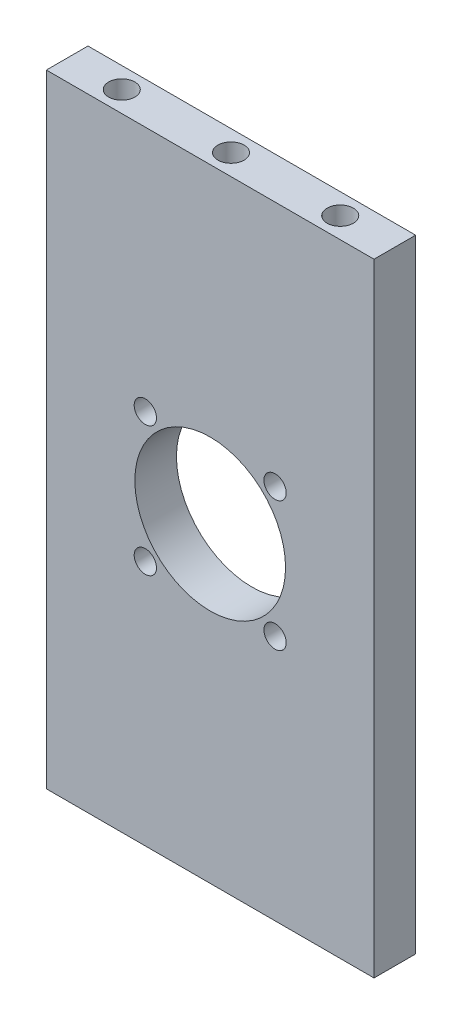
SolidWorks part; units mm, degrees
ref_plane "Front Plane" through (0, 0, 0) normal (0, 0, 1) x (1, 0, 0)
ref_plane "Top Plane" through (0, 0, 0) normal (0, 1, 0) x (1, 0, 0)
ref_plane "Right Plane" through (0, 0, 0) normal (1, 0, 0) x (0, 0, -1)
sketch "Sketch1" plane through (0, 0, 0) normal (0, 0, 1) x (1, 0, 0)
  line L1 (-25, -47.5) -> (25, -47.5)
  line L2 (-25, -47.5) -> (-25, 47.5)
  line L3 (-25, 47.5) -> (25, 47.5)
  line L4 (25, -47.5) -> (25, 47.5)
  line L5 (-25, -47.5) -> (25, 47.5) construction
  line L6 (-25, 47.5) -> (25, -47.5) construction
  point P0 (0, 0)
  dimension "D1" = 95
  dimension "D2" = 50
extrude "Boss-Extrude1" add sketch "Sketch1" against normal blind 6.35
sketch "Sketch2" plane through (0, 47.5, 0) normal (0, 1, 0) x (1, 0, 0)
  point P0 (-16.67, 3.175)
  point P1 (0, 3.175)
  point P2 (16.67, 3.175)
  dimension "D1" = 3.175
  dimension "D2" = 16.67
  dimension "D3" = 16.67
sketch "Sketch3" plane through (0, -47.5, 0) normal (0, -1, 0) x (1, 0, 0)
  line L4 (25, 0) -> (-25, 0)
  line L5 (-25, 0) -> (-25, -6.35)
  line L6 (-25, -6.35) -> (25, -6.35)
  line L7 (25, -6.35) -> (25, 0)
  line L8 (25, 0) -> (-25, 0) construction
  line L9 (-25, 0) -> (-25, -6.35) construction
  line L10 (-25, -6.35) -> (25, -6.35) construction
  line L11 (25, -6.35) -> (25, 0) construction
  point P2 (16.67, -3.175)
  point P6 (0, -3.175)
  point P7 (-16.67, -3.175)
  dimension "D1" = 0
hole_wizard "Ø4.0mm Dowel Hole1" positions "Sketch3" profile "Sketch5" hole size "Ø4.0" standard "ANSI Metric"
sketch "Sketch5" plane through (-16.67, -47.5, -3.175) normal (1, 0, 0) x (0, 0, -1)
  line L0 (0, 0) -> (0, 4.4017)
  line L1 (0, 4.4017) -> (2, 3.2)
  line L2 (2, 3.2) -> (2, 0)
  line L5 (2, 0) -> (0, 0)
  line L10 (0, 4.4017) -> (-2, 3.2) construction
  line L11 (0, -6.35) -> (0, 107.95) construction
  dimension "Hole Dia." = 4
  dimension "Hole Depth" = 3.2
  dimension "Drill Angle" = 118
hole_wizard "Ø4.0mm Dowel Hole2" positions "Sketch2" profile "Sketch6" hole size "Ø4.0" standard "ANSI Metric"
sketch "Sketch6" plane through (-16.67, 47.5, -3.175) normal (1, 0, 0) x (0, 0, 1)
  line L0 (0, 0) -> (0, 4.4017)
  line L1 (0, 4.4017) -> (2, 3.2)
  line L2 (2, 3.2) -> (2, 0)
  line L5 (2, 0) -> (0, 0)
  line L10 (0, 4.4017) -> (-2, 3.2) construction
  line L11 (0, -6.35) -> (0, 107.95) construction
  dimension "Hole Dia." = 4
  dimension "Hole Depth" = 3.2
  dimension "Drill Angle" = 118
sketch "Sketch7" plane through (0, 0, -6.35) normal (0, 0, -1) x (-1, 0, 0)
  circle A0 centre (0, 0) radius 11.5
  dimension "D1" = 23
extrude "Cut-Extrude1" cut sketch "Sketch7" against normal through all
sketch "Sketch8" plane through (0, 0, -6.35) normal (0, 0, -1) x (-1, 0, 0)
  line L0 (0, 0) -> (9.8995, 9.8995) construction
  line L1 (0, 0) -> (0, 14) construction
  circle A0 centre (0, 0) radius 14 construction
  point P3 (9.8995, 9.8995)
  point P9 (9.8995, -9.8995)
  point P10 (-9.8995, -9.8995)
  point P11 (-9.8995, 9.8995)
  point P12 (0, 0)
  dimension "D1" = 28
  dimension "D2" = 45
  dimension "D3" = 4
hole_wizard "M3 Clearance Hole1" positions "Sketch8" profile "Sketch9" hole size "M3" standard "ANSI Metric"
sketch "Sketch9" plane through (9.8995, 9.8995, -6.35) normal (1, 0, 0) x (0, 1, 0)
  line L0 (0, 0) -> (0, 10.5515)
  line L1 (0, 10.5515) -> (1.7, 9.53)
  line L2 (1.7, 9.53) -> (1.7, 0)
  line L5 (1.7, 0) -> (0, 0)
  line L10 (0, 10.5515) -> (-1.7, 9.53) construction
  line L11 (0, -6.35) -> (0, 107.95) construction
  dimension "Hole Dia." = 3.4
  dimension "Hole Depth" = 9.53
  dimension "Drill Angle" = 118
